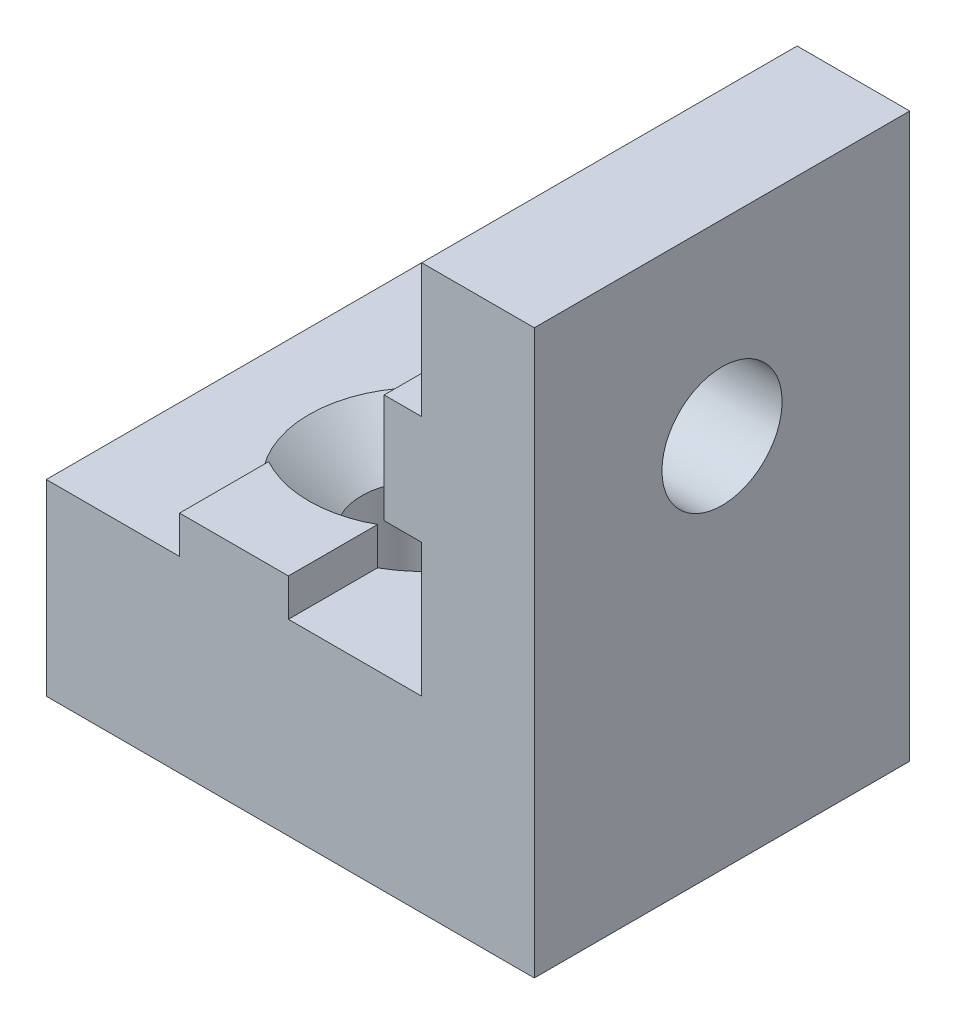
SolidWorks part; units mm, degrees
ref_plane "Front Plane" through (0, 0, 0) normal (0, 0, 1) x (1, 0, 0)
ref_plane "Top Plane" through (0, 0, 0) normal (0, 1, 0) x (1, 0, 0)
ref_plane "Right Plane" through (0, 0, 0) normal (1, 0, 0) x (0, 0, -1)
sketch "Esquisse1" plane through (0, 0, 0) normal (0, 0, 1) x (1, 0, 0)
  line L0 (0, 5) -> (3.55, 5)
  line L1 (3.55, 5) -> (3.55, 6)
  line L2 (3.55, 6) -> (6.45, 6)
  line L3 (6.45, 6) -> (6.45, 5)
  line L4 (6.45, 5) -> (10, 5)
  line L5 (10, 5) -> (10, 8.55)
  line L6 (10, 8.55) -> (9, 8.55)
  line L7 (9, 8.55) -> (9, 11.45)
  line L8 (9, 11.45) -> (10, 11.45)
  line L9 (10, 11.45) -> (10, 15)
  line L10 (10, 15) -> (13, 15)
  line L11 (13, 15) -> (13, 0)
  line L12 (13, 0) -> (0, 0)
  line L13 (0, 0) -> (0, 5)
  point P3 (-6.8358, -2.8214)
  point P15 (-7.4596, -3.1957)
  point P16 (-7.216, -1.6003)
  point P17 (0, 0)
  dimension "D1" = 3
  dimension "D2" = 3.55
  dimension "D3" = 2.9
  dimension "D4" = 5
  dimension "D5" = 1
extrude "Main" add sketch "Esquisse1" along normal blind 10
hole_wizard "Fraisage pour vis à tête fraisée (100) #01" positions "Esquisse3" profile "Esquisse4" countersink size "#0" standard "Ansi Inch" end condition through all
sketch "Esquisse3" plane through (0, 5, 0) normal (0, 1, 0) x (1, 0, 0)
  line L0 (0, -10) -> (0, 0) construction
  line L1 (6.45, -10) -> (3.55, -10) construction
  point P0 (5, -5)
  dimension "D1" = 5
  dimension "D2" = 5
sketch "Esquisse4" plane through (5, 5, 5) normal (1, 0, 0) x (0, 0, 1)
  line L0 (0, 0) -> (0, 5)
  line L1 (0, 5) -> (1.6, 5)
  line L2 (1.6, 5) -> (1.6, 1.1747)
  line L3 (1.6, 1.1747) -> (3, 0)
  line L5 (3, 0) -> (0, 0)
  line L6 (-1.6, 1.1747) -> (-3, 0) construction
  line L11 (0, -6.35) -> (0, 107.95) construction
  dimension "Diamètre du perçage jusqu'au prochain" = 3.2
  dimension "Profondeur du perçage jusqu'au prochain" = 5
  dimension "Diamètre du fraisage entrant" = 6
  dimension "Angle du fraisage entrant" = 100
sketch "Esquisse5" plane through (0, 6, 0) normal (0, 1, 0) x (1, 0, 0)
  circle A0 centre (5, -5) radius 3
  arc A1 (6.45, -7.6263) -> (6.45, -2.3737) centre (5, -5) ccw construction
extrude "Enlèv. mat.-Extru.1" cut sketch "Esquisse5" against normal up to surface (1 mm away) up to face at (7.8917, 5, 5)
sketch "Esquisse6" plane through (9, 0, 0) normal (-1, 0, 0) x (0, 0, 1)
  line L0 (10, 11.45) -> (10, 8.55) construction
  line L1 (10, 15) -> (0, 15) construction
  circle A0 centre (5, 10) radius 1.6
  dimension "D1" = 3.2
  dimension "D2" = 5
  dimension "D3" = 5
extrude "Enlèv. mat.-Extru.2" cut sketch "Esquisse6" against normal through all
